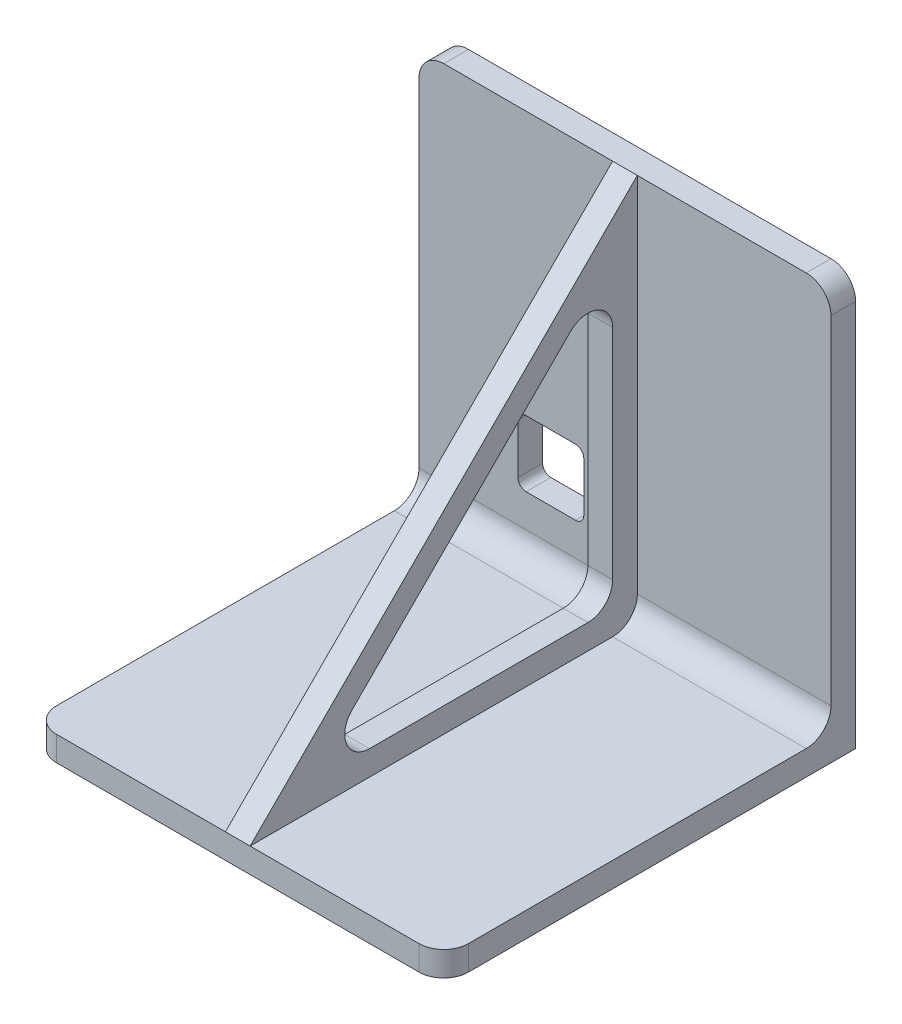
SolidWorks part; units mm, degrees
ref_plane "Front Plane" through (0, 0, 0) normal (0, 0, 1) x (1, 0, 0)
ref_plane "Top Plane" through (0, 0, 0) normal (0, 1, 0) x (1, 0, 0)
ref_plane "Right Plane" through (0, 0, 0) normal (1, 0, 0) x (0, 0, -1)
sketch "Sketch1" plane through (0, 0, 0) normal (0, 1, 0) x (1, 0, 0)
  line L1 (-25, 25) -> (25, 25)
  line L2 (-25, 25) -> (-25, -25)
  line L3 (-25, -25) -> (25, -25)
  line L4 (25, 25) -> (25, -25)
  line L5 (-25, 25) -> (25, -25) construction
  line L6 (-25, -25) -> (25, 25) construction
  point P0 (0, 0)
  dimension "D1" = 50
  dimension "D2" = 50
extrude "Boss-Extrude1" add sketch "Sketch1" along normal blind 3
sketch "Sketch2" plane through (0, 3, 0) normal (0, 1, 0) x (1, 0, 0)
  line L0 (25, -25) -> (25, 25) construction
  line L1 (-25, 25) -> (25, 25)
  line L2 (-25, 25) -> (-25, 22)
  line L3 (-25, 22) -> (25, 22)
  line L4 (25, 25) -> (25, 22)
  dimension "D1" = 3
extrude "Boss-Extrude2" add sketch "Sketch2" along normal offset from surface (47 mm away) 50 up to face at (0, 0, 0)
ref_plane "Plane1" through (0, 0, 0) normal (1, 0, 0) x (0, 0, -1)
sketch "Sketch3" plane through (0, 0, 0) normal (1, 0, 0) x (0, 0, -1)
  line L0 (-25, 3) -> (22, 50)
  line L1 (22, 50) -> (22, 3)
  line L2 (22, 3) -> (-25, 3)
extrude "Boss-Extrude3" add sketch "Sketch3" along normal mid plane 3
sketch "Sketch4" plane through (0, 0, -25) normal (0, 0, -1) x (-1, 0, 0)
  line L0 (9, 10) -> (9, 18) construction
  line L1 (13, 10) -> (5, 10)
  line L2 (13, 10) -> (13, 18)
  line L3 (13, 18) -> (5, 18)
  line L4 (5, 10) -> (5, 18)
  line L5 (25, 50) -> (25, 0) construction
  line L6 (13, 14) -> (5, 14) construction
  line L7 (-25, 0) -> (25, 0) construction
  dimension "D1" = 16
  dimension "D2" = 14
  dimension "D3" = 8
  dimension "D4" = 8
extrude "Cut-Extrude1" cut sketch "Sketch4" against normal up to next
fillet "Fillet1" radius 1 4 edges at (-5, 10, -23.5) (-13, 10, -23.5) (-13, 18, -23.5) (-5, 18, -23.5)
sketch "Sketch5" plane through (-1.5, 0, 0) normal (-1, 0, 0) x (0, 0, 1)
  line L6 (-19, 6) -> (17.7574, 6)
  line L7 (17.7574, 6) -> (-19, 42.7574)
  line L8 (-19, 42.7574) -> (-19, 6)
  line L9 (-19, 6) -> (17.7574, 6)
  line L10 (17.7574, 6) -> (-19, 42.7574)
  line L11 (-19, 42.7574) -> (-19, 6)
  dimension "D1" = 3
extrude "Cut-Extrude2" cut sketch "Sketch5" against normal up to next
fillet "Fillet2" radius 3 9 edges at (13.25, 3, -22) (-13.25, 3, -22) (-25, 50, -23.5) (25, 50, -23.5) (25, 1.5, 25) (-25, 1.5, 25) (0, 6, 17.7574) (0, 42.7574, -19) (0, 6, -19)
